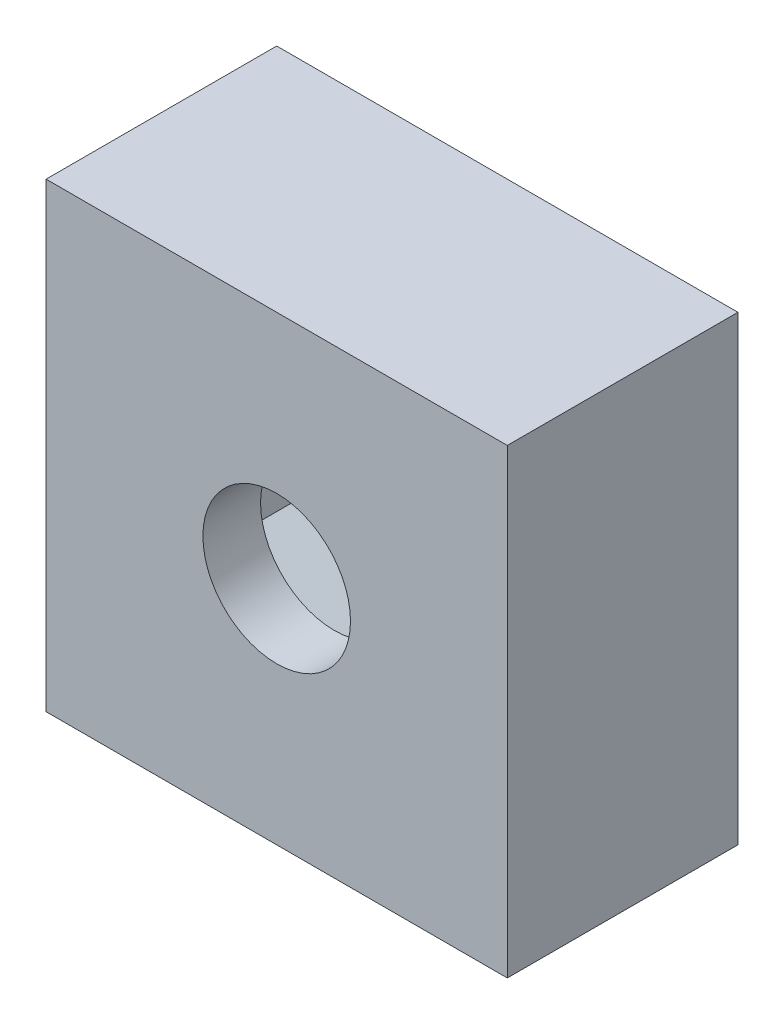
SolidWorks part; units mm, degrees
ref_plane "Front Plane" through (0, 0, 0) normal (0, 0, 1) x (1, 0, 0)
ref_plane "Top Plane" through (0, 0, 0) normal (0, 1, 0) x (1, 0, 0)
ref_plane "Right Plane" through (0, 0, 0) normal (1, 0, 0) x (0, 0, -1)
sketch "Sketch1" plane through (0, 0, 0) normal (0, 0, 1) x (1, 0, 0)
  line L1 (-5, -5) -> (5, -5)
  line L2 (-5, -5) -> (-5, 5)
  line L3 (-5, 5) -> (5, 5)
  line L4 (5, -5) -> (5, 5)
  line L5 (-5, -5) -> (5, 5) construction
  line L6 (-5, 5) -> (5, -5) construction
  line L7 (0, 3.4352) -> (-2.975, 1.7176)
  line L8 (-2.975, 1.7176) -> (-2.975, -1.7176)
  line L9 (-2.975, -1.7176) -> (0, -3.4352)
  line L10 (0, -3.4352) -> (2.975, -1.7176)
  line L11 (2.975, -1.7176) -> (2.975, 1.7176)
  line L12 (2.975, 1.7176) -> (0, 3.4352)
  circle A0 centre (0, 0) radius 2.975 construction
  point P0 (0, 0)
  dimension "D3" = 5.95
  dimension "D1" = 10
  dimension "D2" = 10
extrude "Boss-Extrude1" add sketch "Sketch1" along normal blind 5 contours L1 L4 L3 L2 L12 L11 L10 L9 L8 L7 | L11 L12 L7 L8 L9 L10 region at (-4.8586, 0, 0) region at (0, 0, 0)
extrude "Cut-Extrude1" cut sketch "Sketch1<3>" along normal blind 2.5 from offset 1.25 contours L11 L12 L7 L8 L9 L10 region at (0, 0, 0)
sketch "Sketch1<3>" plane through (0, 0, 0) normal (0, 0, 1) x (1, 0, 0) same geometry as "Sketch1"
sketch "Sketch2" plane through (0, 0, 5) normal (0, 0, 1) x (1, 0, 0)
  circle A0 centre (0, 0) radius 1.6
  dimension "D1" = 3.2
extrude "Cut-Extrude2" cut sketch "Sketch2" against normal through all
